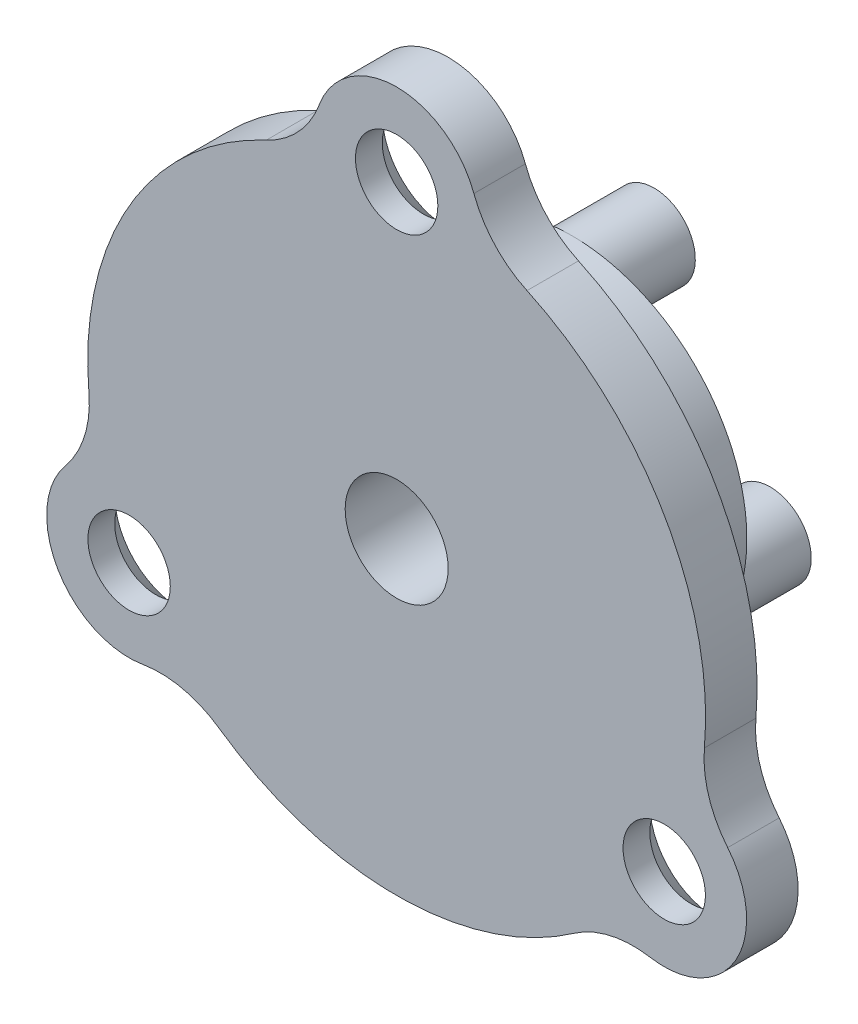
SolidWorks part; units mm, degrees
material "6061 Alloy"
ref_plane "Front" through (0, 0, 0) normal (0, 0, 1) x (1, 0, 0)
ref_plane "Top" through (0, 0, 0) normal (0, 1, 0) x (1, 0, 0)
ref_plane "Right" through (0, 0, 0) normal (1, 0, 0) x (0, 0, -1)
sketch "Sketch1" plane through (0, 0, 0) normal (0, 0, 1) x (1, 0, 0)
  circle A0 centre (0, 0) radius 19
  circle A1 centre (0, 0) radius 2.5
  circle A2 centre (0, 15) radius 2
  circle A3 centre (12.9904, -7.5) radius 2
  circle A4 centre (-12.9904, -7.5) radius 2
  point P13 (0, 0)
  dimension "D3" = 5
  dimension "D4" = 38
  dimension "D5" = 4
  dimension "D1" = 15
  dimension "D2" = 3
extrude "Boss-Extrude1" add sketch "Sketch1" along normal blind 2.5
sketch "Sketch4" plane through (0, 0, 0) normal (0, 0, -1) x (-1, 0, 0)
  circle A0 centre (0, 0) radius 2.5
  circle A1 centre (0, 0) radius 8.5
  circle A2 centre (0, 0) radius 2.5 construction
  dimension "D1" = 17
extrude "Boss-Extrude3" add sketch "Sketch4" along normal blind 6
sketch "Sketch5" plane through (0, 0, 0) normal (0, 0, -1) x (-1, 0, 0)
  circle A0 centre (0, 0) radius 9.25
  circle A1 centre (0, 0) radius 8.5 construction
  circle A2 centre (0, 0) radius 8.5
  dimension "D1" = 0.75
extrude "Boss-Extrude4" add sketch "Sketch5" along normal blind 0.5
chamfer "Chamfer1" distance 1.2 angle 45 3 edges at (14.9904, -7.5, 0) (-10.9904, -7.5, 0) (2, 15, 0)
sketch "Sketch6" plane through (0, 0, -6) normal (0, 0, -1) x (-1, 0, 0)
  line L0 (0, 8.5) -> (0, 2.5) construction
  circle A0 centre (0, 0) radius 8.5 construction
  circle A1 centre (0, 0) radius 2.5 construction
  point P7 (0, 6.5)
  point P8 (5.6292, 3.25)
  point P11 (5.6292, -3.25)
  point P12 (0, -6.5)
  point P13 (-5.6292, -3.25)
  point P14 (-5.6292, 3.25)
  point P15 (0, 0)
  dimension "D2" = 2
  dimension "D1" = 6
sketch "Sketch8" plane through (0, 0, 0) normal (0, 0, -1) x (-1, 0, 0)
  circle A0 centre (0, 0) radius 15
  circle A1 centre (12.9904, -7.5) radius 4
  circle A2 centre (0, 15) radius 4
  circle A3 centre (-12.9904, -7.5) radius 4
  circle A4 centre (0, 0) radius 23.0073
  circle M4 centre (0, 0) radius 19
  dimension "D1" = 30
extrude "Cut-Extrude1" cut sketch "Sketch8" against normal blind 10 contours A2 A0 A1 M4 | A3 A1 A0 M4 | A3 A0 A2 M4 region at (-13.084, 7.554, 0) region at (13.084, 7.554, 0) region at (0, -15.1081, 0)
fillet "Fillet1" radius 5 6 edges at (-10.5464, -10.6665, 1.25) (10.5464, -10.6665, 1.25) (14.5106, -3.8002, 1.25) (3.9643, 14.4667, 1.25) (-3.9643, 14.4667, 1.25) (-14.5106, -3.8002, 1.25)
sketch "Sketch9" plane through (0, 0, -6) normal (0, 0, -1) x (-1, 0, 0)
  circle A0 centre (0, 6.5) radius 2
  circle A2 centre (5.6292, -3.25) radius 2
  circle A4 centre (-5.6292, -3.25) radius 2
  dimension "D1" = 4
  dimension "D3" = 4
  dimension "D5" = 4
extrude "Boss-Extrude5" add sketch "Sketch9" along normal blind 4
